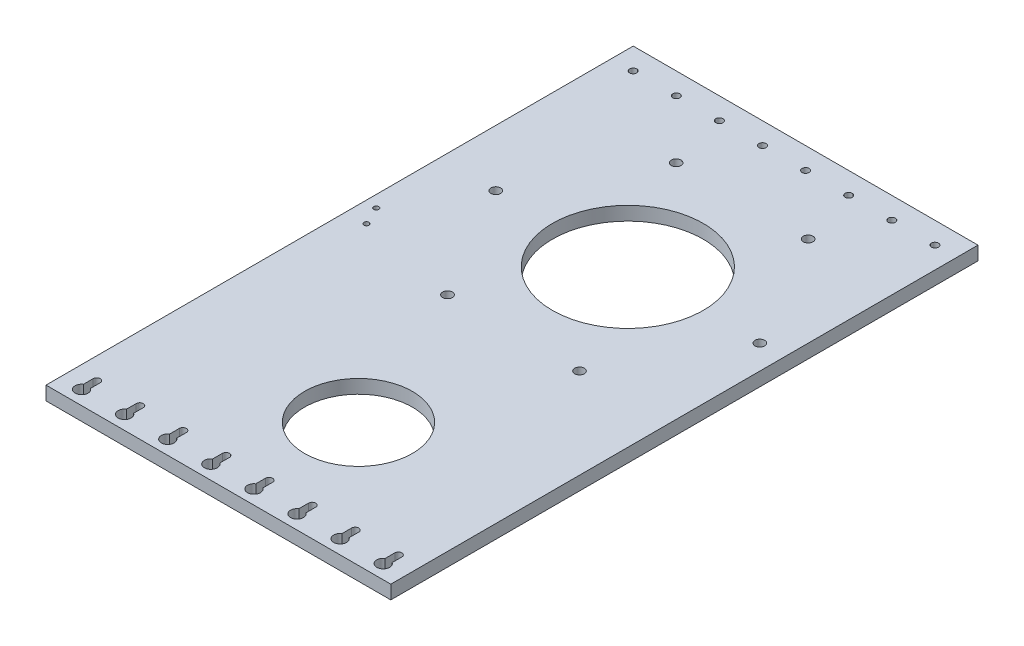
SolidWorks part; units mm, degrees
material "6061 Alloy"
ref_plane "Front Plane" through (0, 0, 0) normal (0, 0, 1) x (1, 0, 0)
ref_plane "Top Plane" through (0, 0, 0) normal (0, 1, 0) x (1, 0, 0)
ref_plane "Right Plane" through (0, 0, 0) normal (1, 0, 0) x (0, 0, -1)
sketch "Sketch1" plane through (0, 0, 0) normal (0, 1, 0) x (1, 0, 0)
  line L0 (87.5, 272.5) -> (87.5, 0) construction
  line L1 (0, 0) -> (160, 0)
  line L2 (0, 0) -> (0, 272.5)
  line L3 (0, 272.5) -> (160, 272.5)
  line L4 (160, 0) -> (160, 272.5)
  line L5 (87.5, 182.5) -> (148.75, 182.5) construction
  line L6 (10, 6.5) -> (10, 13.5) construction
  line L7 (5.4755, 147.7989) -> (9.5163, 139.2011) construction
  line L8 (22, 0) -> (22, 272.5) construction
  line L9 (22, 148.5) -> (0, 148.5) construction
  line L10 (22, 138.5) -> (0, 138.5) construction
  line L11 (0, 148.5) -> (0, 138.5) construction
  line L12 (17.3003, 148.5) -> (22, 138.5) construction
  line L13 (8.35, 6.5) -> (8.35, 13.5)
  line L14 (11.65, 6.5) -> (11.65, 13.5)
  line L15 (10, 262.5) -> (10, 0) construction
  line L16 (31.65, 6.5) -> (31.65, 13.5)
  line L17 (28.35, 6.5) -> (28.35, 13.5)
  line L18 (30, 6.5) -> (30, 13.5) construction
  line L19 (51.65, 6.5) -> (51.65, 13.5)
  line L20 (48.35, 6.5) -> (48.35, 13.5)
  line L21 (50, 6.5) -> (50, 13.5) construction
  line L22 (71.65, 6.5) -> (71.65, 13.5)
  line L23 (68.35, 6.5) -> (68.35, 13.5)
  line L24 (70, 6.5) -> (70, 13.5) construction
  line L25 (91.65, 6.5) -> (91.65, 13.5)
  line L26 (88.35, 6.5) -> (88.35, 13.5)
  line L27 (90, 6.5) -> (90, 13.5) construction
  line L28 (111.65, 6.5) -> (111.65, 13.5)
  line L29 (108.35, 6.5) -> (108.35, 13.5)
  line L30 (110, 6.5) -> (110, 13.5) construction
  line L31 (131.65, 6.5) -> (131.65, 13.5)
  line L32 (128.35, 6.5) -> (128.35, 13.5)
  line L33 (130, 6.5) -> (130, 13.5) construction
  line L34 (151.65, 6.5) -> (151.65, 13.5)
  line L35 (148.35, 6.5) -> (148.35, 13.5)
  line L36 (150, 6.5) -> (150, 13.5) construction
  line L37 (10, 262.5) -> (30, 262.5) construction
  circle A0 centre (87.5, 182.5) radius 35
  circle A1 centre (87.5, 57.5) radius 25
  circle A2 centre (87.5, 182.5) radius 61.25 construction
  circle A3 centre (148.75, 182.5) radius 2.25
  circle A4 centre (118.125, 129.4559) radius 2.25
  circle A5 centre (56.875, 129.4559) radius 2.25
  circle A6 centre (26.25, 182.5) radius 2.25
  circle A7 centre (56.875, 235.5441) radius 2.25
  circle A8 centre (118.125, 235.5441) radius 2.25
  circle A10 centre (5.4755, 147.7989) radius 1.175
  circle A11 centre (9.5163, 139.2011) radius 1.175
  circle A12 centre (87.5, 182.5) radius 78 construction
  circle A13 centre (10, 262.5) radius 1.65
  arc A14 (8.35, 6.5) -> (11.65, 6.5) centre (10, 6.5) ccw
  arc A15 (11.65, 13.5) -> (8.35, 13.5) centre (10, 13.5) ccw
  circle A16 centre (30, 262.5) radius 1.65
  arc A17 (28.35, 6.5) -> (31.65, 6.5) centre (30, 6.5) ccw
  arc A18 (31.65, 13.5) -> (28.35, 13.5) centre (30, 13.5) ccw
  circle A19 centre (50, 262.5) radius 1.65
  arc A20 (48.35, 6.5) -> (51.65, 6.5) centre (50, 6.5) ccw
  arc A21 (51.65, 13.5) -> (48.35, 13.5) centre (50, 13.5) ccw
  circle A22 centre (70, 262.5) radius 1.65
  arc A23 (68.35, 6.5) -> (71.65, 6.5) centre (70, 6.5) ccw
  arc A24 (71.65, 13.5) -> (68.35, 13.5) centre (70, 13.5) ccw
  circle A25 centre (90, 262.5) radius 1.65
  arc A26 (88.35, 6.5) -> (91.65, 6.5) centre (90, 6.5) ccw
  arc A27 (91.65, 13.5) -> (88.35, 13.5) centre (90, 13.5) ccw
  circle A28 centre (110, 262.5) radius 1.65
  arc A29 (108.35, 6.5) -> (111.65, 6.5) centre (110, 6.5) ccw
  arc A30 (111.65, 13.5) -> (108.35, 13.5) centre (110, 13.5) ccw
  circle A31 centre (130, 262.5) radius 1.65
  arc A32 (128.35, 6.5) -> (131.65, 6.5) centre (130, 6.5) ccw
  arc A33 (131.65, 13.5) -> (128.35, 13.5) centre (130, 13.5) ccw
  circle A34 centre (150, 262.5) radius 1.65
  arc A35 (148.35, 6.5) -> (151.65, 6.5) centre (150, 6.5) ccw
  arc A36 (151.65, 13.5) -> (148.35, 13.5) centre (150, 13.5) ccw
  point P15 (87.5, 182.5)
  point P29 (10, 10)
  point P42 (7.4959, 143.5)
  point P43 (0, 143.5)
  point P55 (30, 10)
  point P65 (50, 10)
  point P74 (70, 10)
  point P83 (90, 10)
  point P92 (110, 10)
  point P101 (130, 10)
  point P110 (150, 10)
  dimension "D3" = 70
  dimension "D4" = 50
  dimension "D7" = 122.5
  dimension "D8" = 4.5
  dimension "D11" = 124
  dimension "D13" = 2.35
  dimension "D16" = 156
  dimension "D19" = 3.3
  dimension "D24" = 252.5
  dimension "D1" = 160
  dimension "D2" = 272.5
  dimension "D5" = 125
  dimension "D6" = 90
  dimension "D10" = 61.25
  dimension "D12" = 65.5
  dimension "D14" = 9.5
  dimension "D15" = 10
  dimension "D17" = 11
  dimension "D18" = 72.5
  dimension "D20" = 10
  dimension "D21" = 10
  dimension "D22" = 3.3
  dimension "D23" = 7
  dimension "D26" = 20
  dimension "D25" = 8
  dimension "D9" = 6
extrude "Boss-Extrude1" add sketch "Sketch1" along normal blind 6.35 contours A1 | A0 | A4 | A8 | A7 | A6 | L4 L3 L2 L1 | A3 | A5 | A11 | A10 | A28 | A25 | A31 | A34 | A22 | A19 | A16 | A13 | L14 A15 L13 A14 | L16 A18 L17 A17 | L19 A21 L20 A20 | L22 A24 L23 A23 | L25 A27 L26 A26 | L28 A30 L29 A29 | L31 A33 L32 A32 | L34 A36 L35 A35 region at (87.5, 0, -182.5) region at (87.5, 0, -57.5) region at (118.125, 0, -129.4559) region at (26.25, 0, -182.5) region at (56.875, 0, -235.5441) region at (118.125, 0, -235.5441)
sketch "Sketch2" plane through (0, 6.35, 0) normal (0, 1, 0) x (1, 0, 0)
  line L0 (150, 6.5) -> (130, 6.5) construction
  circle A0 centre (150, 6.5) radius 3
  circle A1 centre (130, 6.5) radius 3
  circle A2 centre (110, 6.5) radius 3
  circle A3 centre (90, 6.5) radius 3
  circle A4 centre (70, 6.5) radius 3
  circle A5 centre (50, 6.5) radius 3
  circle A6 centre (30, 6.5) radius 3
  circle A7 centre (10, 6.5) radius 3
  dimension "D1" = 6
  dimension "D2" = 20
extrude "Cut-Extrude1" cut sketch "Sketch2" against normal up to next
